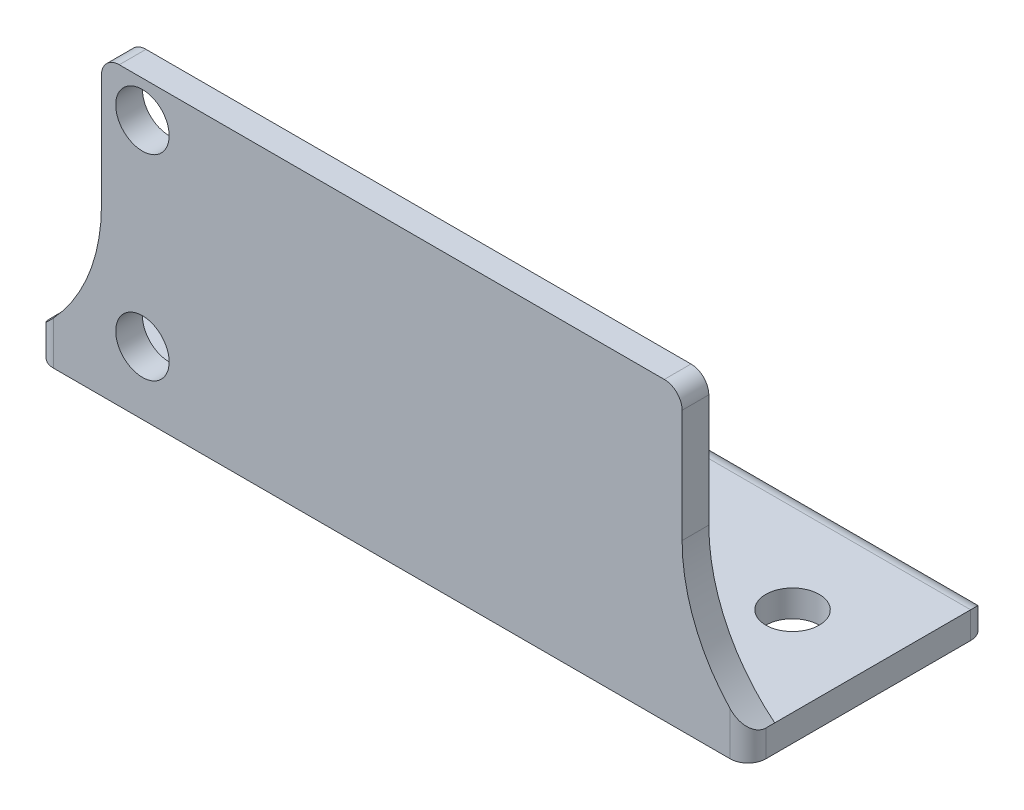
SolidWorks part; units mm, degrees
ref_plane "Front Plane" through (0, 0, 0) normal (0, 0, 1) x (1, 0, 0)
ref_plane "Top Plane" through (0, 0, 0) normal (0, 1, 0) x (1, 0, 0)
ref_plane "Right Plane" through (0, 0, 0) normal (1, 0, 0) x (0, 0, -1)
sketch "Sketch1" plane through (0, 0, 0) normal (0, 0, 1) x (1, 0, 0)
  line L1 (-16.3, 7.55) -> (16.3, 7.55)
  line L2 (-16.3, 7.55) -> (-16.3, -7.55)
  line L3 (-16.3, -7.55) -> (16.3, -7.55)
  line L4 (16.3, 7.55) -> (16.3, -7.55)
  circle A0 centre (-14, 5.5) radius 1.5
  circle A1 centre (-14, -5.5) radius 1.5
extrude "Boss-Extrude1" add sketch "Sketch1" along normal blind 1.5
sketch "Sketch2" plane through (0, -7.55, 0) normal (0, -1, 0) x (1, 0, 0)
  line L1 (-20, 1.5) -> (20, 1.5)
  line L2 (-20, 1.5) -> (-20, -12)
  line L3 (-20, -12) -> (20, -12)
  line L4 (20, 1.5) -> (20, -12)
  circle A0 centre (-15, -6) radius 1.5
  circle A1 centre (15, -6) radius 1.5
extrude "Boss-Extrude2" add sketch "Sketch2" along normal blind 1.5
fillet "Fillet1" radius 10 2 edges at (16.3, -7.55, 0.75) (-16.3, -7.55, 0.75)
fillet "Fillet2" radius 1 7 edges at (-20, -8.3, 1.5) (20, -8.3, 1.5) (16.3, 7.55, 0.75) (-16.3, 7.55, 0.75) (0, -7.55, -12) (-20, -8.3, -12) (20, -8.3, -12)
